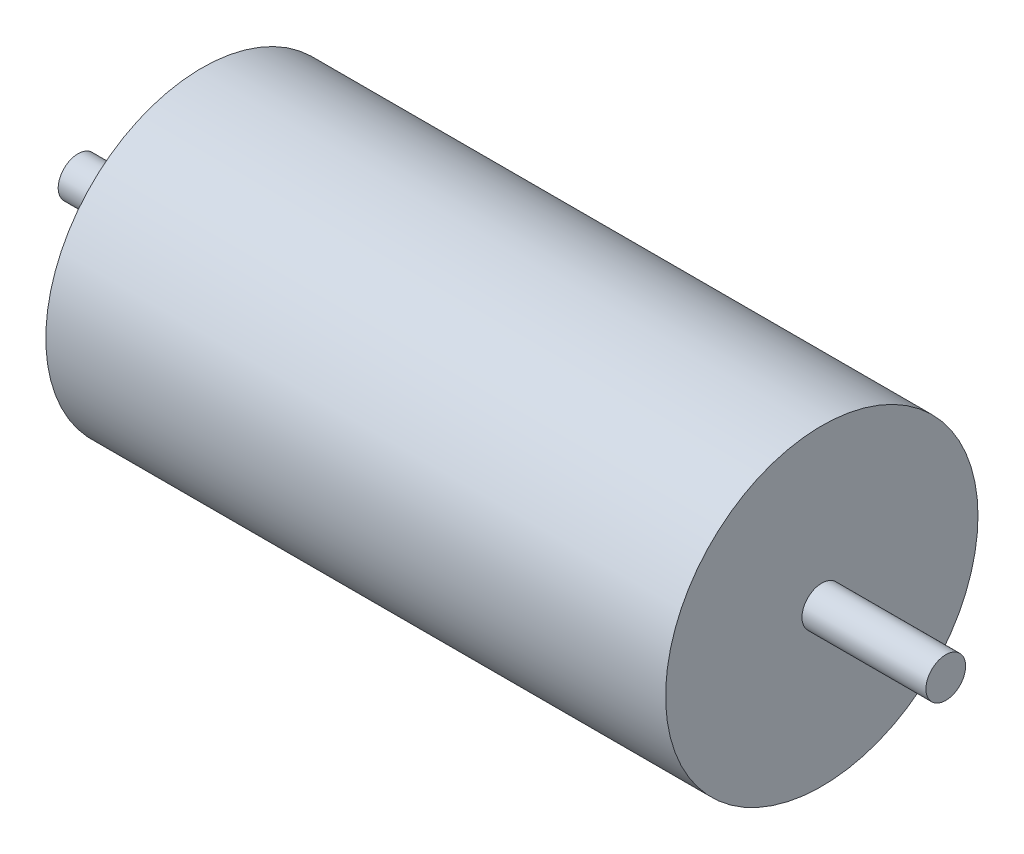
SolidWorks part; units mm, degrees
ref_plane "Front Plane" through (0, 0, 0) normal (0, 0, 1) x (1, 0, 0)
ref_plane "Top Plane" through (0, 0, 0) normal (0, 1, 0) x (1, 0, 0)
ref_plane "Right Plane" through (0, 0, 0) normal (1, 0, 0) x (0, 0, -1)
sketch "Sketch1" plane through (0, 0, 0) normal (1, 0, 0) x (0, 0, -1)
  circle A0 centre (0, 0) radius 31.5
  circle A1 centre (0, 0) radius 4
  dimension "D1" = 63
  dimension "D2" = 8
extrude "Boss-Extrude1" add sketch "Sketch1" along normal blind 125
extrude "Boss-Extrude2" add sketch "Sketch1<2>" along normal blind 150 and the other way blind 25 contours A1 region at (0, 0, 0)
sketch "Sketch1<2>" plane through (0, 0, 0) normal (1, 0, 0) x (0, 0, -1) same geometry as "Sketch1"
